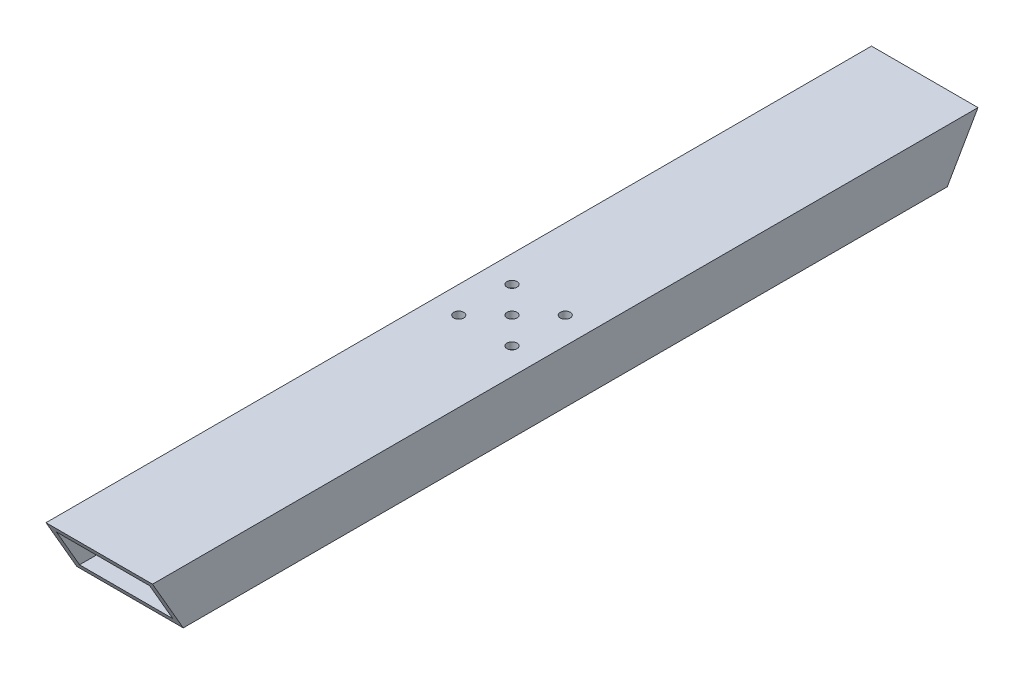
SolidWorks part; units mm, degrees
ref_plane "Front Plane" through (0, 0, 0) normal (0, 0, 1) x (1, 0, 0)
ref_plane "Top Plane" through (0, 0, 0) normal (0, 1, 0) x (1, 0, 0)
ref_plane "Right Plane" through (0, 0, 0) normal (1, 0, 0) x (0, 0, -1)
sketch "Sketch1" plane through (0, 0, 0) normal (0, 0, 1) x (1, 0, 0)
  line L0 (-22.225, 9.525) -> (22.225, 9.525)
  line L1 (-25.4, -12.7) -> (25.4, -12.7)
  line L2 (-25.4, -12.7) -> (-25.4, 12.7)
  line L3 (-25.4, 12.7) -> (25.4, 12.7)
  line L4 (25.4, -12.7) -> (25.4, 12.7)
  line L5 (-25.4, -12.7) -> (25.4, 12.7) construction
  line L6 (-25.4, 12.7) -> (25.4, -12.7) construction
  line L7 (22.225, -9.525) -> (22.225, 9.525)
  line L8 (-22.225, -9.525) -> (22.225, -9.525)
  line L9 (-22.225, -9.525) -> (-22.225, 9.525)
  point P0 (0, 0)
  dimension "D1" = 50.8
  dimension "D2" = 25.4
  dimension "D3" = 3.175
extrude "Boss-Extrude1" add sketch "Sketch1" along normal blind 393.7
sketch "Sketch2" plane through (25.4, 0, 0) normal (1, 0, 0) x (0, 0, -1)
  line L0 (0, 12.7) -> (-14.6647, -12.7)
  line L1 (-393.7, -12.7) -> (0, -12.7) construction
  line L2 (-14.6647, -12.7) -> (0, -12.7)
  line L3 (0, -12.7) -> (0, 12.7)
  line L4 (-196.85, 12.7) -> (-196.85, -12.7) construction
  line L5 (-393.7, 12.7) -> (0, 12.7) construction
  line L6 (-393.7, -12.7) -> (-393.7, 12.7)
  line L7 (-379.0353, -12.7) -> (-393.7, -12.7)
  line L8 (-393.7, 12.7) -> (-379.0353, -12.7)
  dimension "D1" = 30
extrude "Cut-Extrude1" cut sketch "Sketch2" against normal blind 457.2
sketch "Sketch3" plane through (0, -12.7, 0) normal (0, -1, 0) x (-1, 0, 0)
  line L0 (25.4, -196.85) -> (-25.4, -196.85) construction
  line L1 (25.4, -379.0353) -> (25.4, -14.6647) construction
  line L2 (-25.4, -379.0353) -> (-25.4, -14.6647) construction
  line L3 (0, -379.0353) -> (0, -14.6647) construction
  line L4 (25.4, -379.0353) -> (-25.4, -379.0353) construction
  line L5 (25.4, -14.6647) -> (-25.4, -14.6647) construction
  circle A0 centre (0, -196.85) radius 2.3812
  circle A1 centre (-12.7, -209.55) radius 2.3812
  circle A2 centre (12.7, -209.55) radius 2.3812
  circle A3 centre (-12.7, -184.15) radius 2.3812
  circle A4 centre (12.7, -184.15) radius 2.3812
  dimension "D1" = 4.7625
  dimension "D2" = 4.7625
  dimension "D3" = 12.7
  dimension "D4" = 12.7
extrude "Cut-Extrude2" cut sketch "Sketch3" against normal through all
sketch "Sketch4" plane through (-25.4, 0, 0) normal (-1, 0, 0) x (0, 0, 1)
  line L0 (196.85, -12.7) -> (196.85, 12.7) construction
  line L1 (379.0353, -12.7) -> (14.6647, -12.7) construction
  line L2 (393.7, 12.7) -> (0, 12.7) construction
  circle A0 centre (196.85, 0) radius 2.3813
  circle A1 centre (209.55, 0) radius 2.3813
  circle A2 centre (184.15, 0) radius 2.3813
  dimension "D1" = 4.7625
  dimension "D2" = 2
extrude "Cut-Extrude3" cut sketch "Sketch4" against normal blind 3.175
